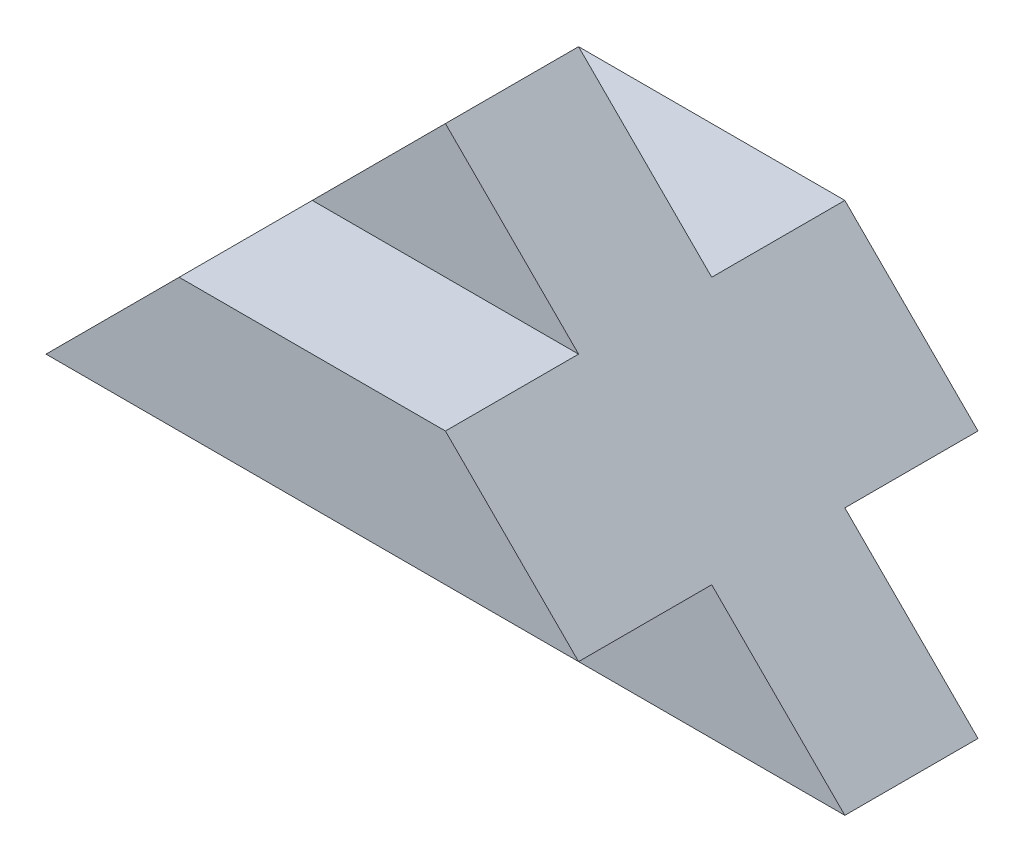
SolidWorks part; units mm, degrees
ref_plane "Front Plane" through (0, 0, 0) normal (0, 0, 1) x (1, 0, 0)
ref_plane "Top Plane" through (0, 0, 0) normal (0, 1, 0) x (1, 0, 0)
ref_plane "Right Plane" through (0, 0, 0) normal (1, 0, 0) x (0, 0, -1)
sketch "Sketch1" plane through (0, 0, 0) normal (1, 0, 0) x (0, 0, -1)
  line L0 (0, 152.4) -> (0, 0)
  line L1 (-76.2, 76.2) -> (76.2, 76.2)
  dimension "D1" = 152.4
  dimension "D2" = 76.2
  dimension "D3" = 76.2
extrude "Extrude-Thin1" add sketch "Sketch1" along normal blind 304.8 thin contours L1 | L0 thin type mid plane wall 50.8
chamfer "Chamfer1" distance 152.4 angle 45 2 edges at (304.8, 152.4, 0) (0, 152.4, 0)
equation "\"D2@Sketch1\"=\"D1@Sketch1\"/2"
equation "\"D3@Sketch1\"=\"D2@Sketch1\""
